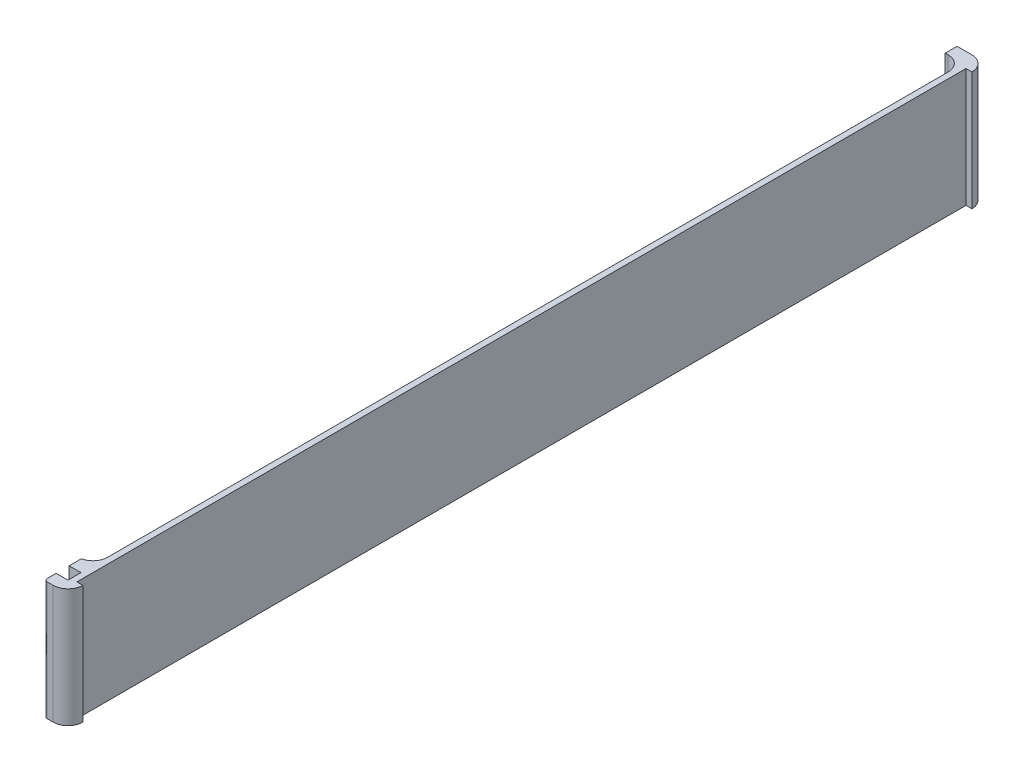
SolidWorks part; units mm, degrees
ref_plane "Front Plane" through (0, 0, 0) normal (0, 0, 1) x (1, 0, 0)
ref_plane "Top Plane" through (0, 0, 0) normal (0, 1, 0) x (1, 0, 0)
ref_plane "Right Plane" through (0, 0, 0) normal (1, 0, 0) x (0, 0, -1)
sketch "Sketch1" plane through (0, 0, 0) normal (0, 1, 0) x (1, 0, 0)
  line L1 (-19.5, 77.5) -> (19.5, 77.5)
  line L2 (-19.5, 77.5) -> (-19.5, -77.5)
  line L3 (-19.5, -77.5) -> (19.5, -77.5)
  line L4 (19.5, 77.5) -> (19.5, -77.5)
  line L5 (-19.5, 77.5) -> (19.5, -77.5) construction
  line L6 (-19.5, -77.5) -> (19.5, 77.5) construction
  point P0 (0, 0)
  dimension "D1" = 39
  dimension "D2" = 155
extrude "Boss-Extrude1" add sketch "Sketch1" along normal blind 2
sketch "Sketch2" plane through (0, 2, 0) normal (0, 1, 0) x (1, 0, 0)
  line L0 (-17.5, -75.5) -> (-17.5, -77.5)
  line L1 (-19.5, 77.5) -> (19.5, 77.5)
  line L2 (-19.5, 77.5) -> (-19.5, -77.5)
  line L3 (-19.5, -77.5) -> (19.5, -77.5)
  line L4 (19.5, 77.5) -> (19.5, -77.5)
  line L5 (-17.5, 75.5) -> (17.5, 75.5)
  line L6 (-17.5, 75.5) -> (-17.5, -75.5)
  line L7 (-17.5, -75.5) -> (17.5, -75.5)
  line L8 (17.5, 75.5) -> (17.5, -75.5)
  line L9 (-17.5, 75.5) -> (17.5, -75.5) construction
  line L10 (-17.5, -75.5) -> (17.5, 75.5) construction
  line L11 (17.5, -75.5) -> (17.5, -77.5)
  point P6 (0, 0)
  line M9 (19.5, -77.5) -> (19.5, 77.5)
  line M10 (19.5, 77.5) -> (-19.5, 77.5)
  line M11 (-19.5, 77.5) -> (-19.5, -77.5)
  line M12 (-19.5, -77.5) -> (19.5, -77.5)
  dimension "D1" = 2
  dimension "D2" = 2
extrude "Boss-Extrude2" add sketch "Sketch2" along normal blind 38 contours L8 L11 L3 L0 L6 L5 M9 M10 M11 M12 region at (-19.0983, 2, 76.5)
sketch "Sketch3" plane through (0, 2, 0) normal (0, 1, 0) x (1, 0, 0)
  line L0 (-17.5, 75.5) -> (-17.5, -77.5) construction
  line L1 (-17.5, -77.5) -> (-15.5, -77.5)
  line L2 (-17.5, -77.5) -> (-17.5, -75.5)
  line L3 (-17.5, -75.5) -> (-15.5, -75.5)
  line L4 (-15.5, -77.5) -> (-15.5, -75.5)
  line L5 (-17.5, -73.3) -> (-15.5, -73.3)
  line L6 (-17.5, -73.3) -> (-17.5, -71.3)
  line L7 (-17.5, -71.3) -> (-15.5, -71.3)
  line L8 (-15.5, -73.3) -> (-15.5, -71.3)
  line L9 (17.5, 75.5) -> (17.5, -77.5) construction
  line L10 (17.5, -77.5) -> (15.5, -77.5)
  line L11 (17.5, -77.5) -> (17.5, -75.5)
  line L12 (17.5, -75.5) -> (15.5, -75.5)
  line L13 (15.5, -77.5) -> (15.5, -75.5)
  line L14 (17.5, -73.3) -> (15.5, -73.3)
  line L15 (17.5, -73.3) -> (17.5, -71.3)
  line L16 (17.5, -71.3) -> (15.5, -71.3)
  line L17 (15.5, -73.3) -> (15.5, -71.3)
  line L18 (15.5, -75.5) -> (15.5, -73.3) construction
  line L19 (-15.5, -73.3) -> (15.5, -73.3) construction
  line L20 (-15.5, -75.5) -> (-15.5, -73.3) construction
  line L21 (-15.5, -75.5) -> (15.5, -75.5) construction
  line L22 (15.5, -71.3) -> (-15.5, -71.3) construction
  dimension "D1" = 2
  dimension "D2" = 2
  dimension "D3" = 2.2
  dimension "D4" = 2
extrude "Boss-Extrude3" add sketch "Sketch3" along normal up to surface (38 mm away) up to face at (0, 40, 0.5)
sketch "Sketch4" plane through (0, 0, -75.5) normal (0, 0, 1) x (1, 0, 0)
  line L0 (-17.5, 40) -> (-15.5, 40)
  line L1 (-17.5, 40) -> (17.5, 40) construction
  line L2 (-15.5, 40) -> (-15.5, 38)
  line L3 (-15.5, 38) -> (-17.5, 38)
  line L5 (-17.5, 38) -> (-17.5, 40)
  line L7 (-17.5, 40) -> (-17.5, 2) construction
  line L8 (-15.5, 33.8) -> (-17.5, 31.8)
  line L9 (-17.5, 31.8) -> (-17.5, 35.8)
  line L10 (-15.5, 33.8) -> (-15.5, 35.8)
  line L11 (-15.5, 35.8) -> (-17.5, 35.8)
  line L12 (0, 0) -> (0, 40) construction
  line L13 (15.5, 35.8) -> (17.5, 35.8)
  line L14 (15.5, 33.8) -> (15.5, 35.8)
  line L15 (17.5, 31.8) -> (17.5, 35.8)
  line L16 (15.5, 33.8) -> (17.5, 31.8)
  line L17 (17.5, 38) -> (17.5, 40)
  line L18 (15.5, 38) -> (17.5, 38)
  line L19 (15.5, 40) -> (15.5, 38)
  line L20 (17.5, 40) -> (15.5, 40)
  dimension "D1" = 2
  dimension "D2" = 2
  dimension "D3" = 45
  dimension "D4" = 2.2
  dimension "D5" = 2
extrude "Boss-Extrude4" add sketch "Sketch4" along normal up to surface (153 mm away)
sketch "Sketch5" plane through (0, 2, 0) normal (0, 1, 0) x (1, 0, 0)
  line L1 (-15.5, -77.5) -> (15.5, -77.5)
  line L2 (-15.5, -77.5) -> (-15.5, -75.5)
  line L3 (-15.5, -75.5) -> (15.5, -75.5)
  line L4 (15.5, -77.5) -> (15.5, -75.5)
  line L5 (-15.5, -71.3) -> (15.5, -71.3)
  line L6 (-15.5, -71.3) -> (-15.5, -73.3)
  line L7 (-15.5, -73.3) -> (15.5, -73.3)
  line L8 (15.5, -71.3) -> (15.5, -73.3)
sketch "Sketch6" plane through (0, 0, -75.5) normal (0, 0, 1) x (1, 0, 0)
  line L0 (-17.5, 38) -> (-15.5, 38) construction
  line L1 (-17.5, 38) -> (17.5, 38)
  line L2 (-17.5, 38) -> (-17.5, 35.8)
  line L3 (-17.5, 35.8) -> (17.5, 35.8)
  line L4 (17.5, 38) -> (17.5, 35.8)
  line L5 (-17.5, 38) -> (-17.5, 35.8) construction
  line L6 (-15.5, 35.8) -> (-17.5, 35.8) construction
extrude "Cut-Extrude1" cut sketch "Sketch6" along normal through all
sketch "Sketch7" plane through (0, 2, 0) normal (0, 1, 0) x (1, 0, 0)
  line L1 (-17.5, -75.5) -> (17.5, -75.5)
  line L2 (-17.5, -75.5) -> (-17.5, -73.3)
  line L3 (-17.5, -73.3) -> (17.5, -73.3)
  line L4 (17.5, -75.5) -> (17.5, -73.3)
extrude "Cut-Extrude2" cut sketch "Sketch7" along normal through all
extrude "Boss-Extrude5" add sketch "Sketch5" along normal blind 2
sketch "Sketch8" plane through (0, 0, 0) normal (1, 0, 0) x (0, 0, -1)
  line L0 (75.5, 40) -> (73.5, 40)
  line L1 (-73.3, 40) -> (75.5, 40) construction
  line L2 (73.5, 40) -> (73.5, 38)
  line L3 (-73.3, 38) -> (75.5, 38) construction
  line L4 (73.5, 38) -> (75.5, 38)
  line L5 (75.5, 38) -> (75.5, 40)
  line L6 (75.5, 35.8) -> (73.5, 35.8)
  line L7 (-73.3, 35.8) -> (75.5, 35.8) construction
  line L8 (73.5, 35.8) -> (73.5, 33.8)
  line L9 (-71.3, 33.8) -> (75.5, 33.8) construction
  line L10 (73.5, 33.8) -> (75.5, 31.8)
  line L11 (75.5, 31.8) -> (75.5, 35.8)
  dimension "D1" = 2
extrude "Boss-Extrude6" add sketch "Sketch8" along normal up to surface and the other way up to surface up to face at (17.5, 16.9, -2.1) other way up to face at (-17.5, 16.9, -2.1)
sketch "Sketch10" plane through (-17.5, 0, 0) normal (1, 0, 0) x (0, 0, -1)
  line L1 (-75.5, 35.8) -> (-77.5, 35.8)
  line L2 (-75.5, 35.8) -> (-75.5, 38)
  line L3 (-75.5, 38) -> (-77.5, 38)
  line L4 (-77.5, 35.8) -> (-77.5, 38)
  line L5 (-73.3, 40) -> (-75.5, 40)
  line L6 (-73.3, 40) -> (-73.3, 38)
  line L7 (-73.3, 38) -> (-75.5, 38)
  line L8 (-75.5, 40) -> (-75.5, 38)
  line M1 (-75.5, 40) -> (-75.5, 38)
  line M2 (-75.5, 38) -> (-77.5, 38)
  line M3 (-77.5, 38) -> (-77.5, 35.8)
  line M4 (-77.5, 35.8) -> (-75.5, 35.8)
  line M11 (-73.3, 38) -> (-73.3, 40)
  line M12 (-73.3, 40) -> (-75.5, 40)
extrude "Boss-Extrude8" add sketch "Sketch10" along normal up to surface (2 mm away) contours L2 M4 M2 M3 | L7 M11 M12 M1 region at (-17.5, 39, 74.4) region at (-17.5, 36.9, 76.5) up to face at (-15.5, 39, -0.1)
sketch "Sketch11" plane through (17.5, 0, 0) normal (-1, 0, 0) x (0, 0, 1)
  line L1 (75.5, 35.8) -> (77.5, 35.8)
  line L2 (75.5, 35.8) -> (75.5, 38)
  line L3 (75.5, 38) -> (77.5, 38)
  line L4 (77.5, 35.8) -> (77.5, 38)
  line L5 (73.3, 40) -> (75.5, 40)
  line L6 (73.3, 40) -> (73.3, 38)
  line L7 (73.3, 38) -> (75.5, 38)
  line L8 (75.5, 40) -> (75.5, 38)
  line M2 (75.5, 35.8) -> (77.5, 35.8)
  line M3 (77.5, 35.8) -> (77.5, 38)
  line M4 (77.5, 38) -> (75.5, 38)
  line M5 (75.5, 38) -> (75.5, 40)
  line M6 (75.5, 40) -> (73.3, 40)
  line M7 (73.3, 40) -> (73.3, 38)
extrude "Boss-Extrude9" add sketch "Sketch11" along normal up to surface (2 mm away) contours L2 M2 M3 M4 | L7 M7 M5 M6 region at (17.5, 36.9, 76.5) region at (17.5, 39, 74.4) up to face at (15.5, 39, -0.1)
fillet "Fillet2" radius 2.5 17 edges at (-17.5, 16.9, 71.3) (17.5, 16.9, 71.3) (19.5, 20, 77.5) (-19.5, 20, 77.5) (-19.5, 20, -77.5) (-17.5, 16.9, -75.5) (17.5, 16.9, -75.5) (19.5, 20, -77.5) (-19.5, 40, 0) (0, 40, -77.5) (19.5, 40, 0) (0, 0, -77.5) (0, 0, 77.5) (-19.5, 0, 0) (19.5, 0, 0) (-17.5, 40, 77.5) (17.5, 40, 77.5)
sketch "Sketch13" plane through (0, 0, -77.5) normal (0, 0, -1) x (-1, 0, 0)
  line L0 (15.5, 37.5) -> (15.5, 4) construction
  line L1 (-15.5, 7) -> (15.5, 7)
  line L2 (-15.5, 7) -> (-15.5, 4)
  line L3 (-15.5, 4) -> (15.5, 4)
  line L4 (15.5, 7) -> (15.5, 4)
  dimension "D1" = 3
sketch "Sketch14" plane through (0, 0, -75.5) normal (0, 0, 1) x (1, 0, 0)
  line L1 (-18.25, 9) -> (18.25, 9)
  line L2 (-18.25, 9) -> (-18.25, 1.25)
  line L3 (-18.25, 1.25) -> (18.25, 1.25)
  line L4 (18.25, 9) -> (18.25, 1.25)
  line L5 (15.5, 7) -> (-15.5, 7) construction
  line L7 (17, 0) -> (17, 2.5) construction
  line L8 (19.5, 2.5) -> (17, 2.5) construction
  line L10 (-19.5, 2.5) -> (-17, 2.5) construction
  point P20 (17, 1.25)
  point P23 (18.25, 2.5)
  point P26 (-18.25, 2.5)
  dimension "D1" = 2
extrude "Boss-Extrude10" add sketch "Sketch14" along normal blind 2
extrude "Cut-Extrude4" cut sketch "Sketch13" against normal blind 2
fillet "Fillet3" radius 2 1 edges at (0, 9, -73.5)
fillet "Fillet4" radius 0.5 12 edges at (0, 4, -77.5) (0, 7, -77.5) (15.5, 7, -76.5) (15.5, 4, -76.5) (15.5, 5.5, -77.5) (-15.5, 4, -76.5) (-15.5, 7, -76.5) (-15.5, 5.5, -77.5) (0, 7, -75.5) (-15.5, 5.5, -75.5) (0, 4, -75.5) (15.5, 5.5, -75.5)
sketch "Sketch15" plane through (0, 0, 0) normal (0, -1, 0) x (1, 0, 0)
  line L0 (0, 77.5) -> (0, 0) construction
  line L1 (-17, 77.5) -> (17, 77.5) construction
  line L2 (0, 0) -> (0, -77.5) construction
  line L4 (17, -77.5) -> (-17, -77.5) construction
  circle A0 centre (0, 38.75) radius 5.1
  circle A1 centre (0, -38.75) radius 5.1
  dimension "D1" = 10.2
extrude "Cut-Extrude5" cut sketch "Sketch15" against normal through all
sketch "Sketch16" plane through (0, 2, 0) normal (0, 1, 0) x (1, 0, 0)
  circle A0 centre (0, 38.75) radius 7.1
  circle A1 centre (0, -38.75) radius 7.1
  circle A2 centre (0, 38.75) radius 5.1 construction
  dimension "D1" = 2
extrude "Boss-Extrude11" add sketch "Sketch16" along normal blind 1
fillet "Fillet5" radius 0.5 4 edges at (0, 2, 45.85) (0, 2, -31.65) (0, 3, 45.85) (0, 3, -31.65)
sketch "Sketch12" plane through (0, 0, -75.5) normal (0, 0, 1) x (1, 0, 0)
  line L0 (0, 0) -> (0, 40) construction
  line L1 (15.5, 40) -> (-15.5, 40) construction
  line L2 (0, 20) -> (-10, 20)
  line L3 (0, 20) -> (-9.0097, 15.6612)
  line L4 (0, 20) -> (-6.2349, 12.1817)
  line L5 (0, 20) -> (-2.2252, 10.2507)
  line L6 (0, 20) -> (2.2252, 10.2507)
  line L7 (0, 20) -> (6.2349, 12.1817)
  line L8 (0, 20) -> (9.0097, 15.6612)
  line L9 (0, 20) -> (10, 20)
  line L10 (0, 20) -> (9.0097, 24.3388)
  line L11 (0, 20) -> (6.2349, 27.8183)
  line L12 (0, 20) -> (2.2252, 29.7493)
  line L13 (0, 20) -> (-2.2252, 29.7493)
  line L14 (0, 20) -> (-6.2349, 27.8183)
  line L15 (0, 20) -> (-9.0097, 24.3388)
  circle A0 centre (0, 20) radius 10
  circle A1 centre (0, 20) radius 7.5
  circle A2 centre (0, 20) radius 5
  circle A3 centre (0, 20) radius 2.5
  point P26 (0, 20)
  dimension "D1" = 20
  dimension "D2" = 2.5
  dimension "D3" = 2.5
  dimension "D4" = 2.5
  dimension "D5" = 14
extrude "Cut-Extrude3" cut sketch "Sketch12" against normal through all contours A1 L6 A0 L7 | A1 L4 A0 L5 | A1 L2 A0 L3 | A1 L14 A0 L15 | A1 L0 A0 L13 | L0 A1 L12 A0 | A1 L10 A0 L11 | A1 L8 A0 L9 | A3 L8 A2 L9 | A3 L10 A2 L11 | L0 A3 L12 A2 | A3 L0 A2 L13 | A3 L14 A2 L15 | A3 L2 A2 L3 | A3 L4 A2 L5 | A3 L6 A2 L7 region at (-3.7903, 12.1293, -75.5) region at (3.7903, 12.1293, -75.5) region at (-1.6732, 16.5256, -75.5) region at (1.6732, 16.5256, -75.5) region at (-8.5168, 18.0561, -75.5) region at (8.5168, 18.0561, -75.5) region at (-0.4345, 23.8563, -75.5) region at (0.4345, 23.8563, -75.5) region at (-3.7596, 19.1419, -75.5) region at (3.7596, 19.1419, -75.5) region at (3.015, 22.4044, -75.5) region at (-3.015, 22.4044, -75.5) region at (-6.8299, 25.4467, -75.5) region at (6.8299, 25.4467, -75.5) region at (-0.9843, 28.7358, -75.5) region at (0.9843, 28.7358, -75.5)
fillet "Fillet6" radius 0.4 112 edges at (5.4555, 26.841, -77.5) (7.8183, 26.2349, -77.5) (7.8835, 23.7965, -77.5) (5.8637, 24.6762, -77.5) (3.75, 20, -77.5) (4.8746, 18.8874, -77.5) (3.3786, 18.3729, -77.5) (2.4373, 19.4437, -77.5) (-1.9471, 28.5306, -77.5) (0, 30, -77.5) (1.9471, 28.5306, -77.5) (0, 27.5, -77.5) (-7.8835, 16.2035, -77.5) (-9.7493, 17.7748, -77.5) (-8.75, 20, -77.5) (-7.312, 18.3311, -77.5) (2.3381, 17.0681, -77.5) (2.1694, 15.4952, -77.5) (0.8345, 16.344, -77.5) (1.0847, 17.7476, -77.5) (-0.8345, 16.344, -77.5) (-2.1694, 15.4952, -77.5) (-2.3381, 17.0681, -77.5) (-1.0847, 17.7476, -77.5) (5.4555, 13.159, -77.5) (4.3388, 10.9903, -77.5) (1.9471, 11.4694, -77.5) (3.2541, 13.2427, -77.5) (0, 22.5, -77.5) (-0.8345, 23.656, -77.5) (0, 25, -77.5) (0.8345, 23.656, -77.5) (-3.3786, 21.6271, -77.5) (-3.9092, 23.1174, -77.5) (-2.3381, 22.9319, -77.5) (-1.9546, 21.5587, -77.5) (-3.3786, 18.3729, -77.5) (-4.8746, 18.8874, -77.5) (-3.75, 20, -77.5) (-2.4373, 19.4437, -77.5) (-1.9471, 11.4694, -77.5) (-4.3388, 10.9903, -77.5) (-5.4555, 13.159, -77.5) (-3.2541, 13.2427, -77.5) (-7.8835, 23.7965, -77.5) (-7.8183, 26.2349, -77.5) (-5.4555, 26.841, -77.5) (-5.8637, 24.6762, -77.5) (2.3381, 22.9319, -77.5) (3.9092, 23.1174, -77.5) (3.3786, 21.6271, -77.5) (1.9546, 21.5587, -77.5) (8.75, 20, -77.5) (9.7493, 17.7748, -77.5) (7.8835, 16.2035, -77.5) (7.312, 18.3311, -77.5) (7.8835, 23.7965, -75.5) (7.8183, 26.2349, -75.5) (5.4555, 26.841, -75.5) (5.8637, 24.6762, -75.5) (3.3786, 18.3729, -75.5) (4.8746, 18.8874, -75.5) (3.75, 20, -75.5) (2.4373, 19.4437, -75.5) (1.9471, 28.5306, -75.5) (0, 30, -75.5) (-1.9471, 28.5306, -75.5) (0, 27.5, -75.5) (-8.75, 20, -75.5) (-9.7493, 17.7748, -75.5) (-7.8835, 16.2035, -75.5) (-7.312, 18.3311, -75.5) (0.8345, 16.344, -75.5) (2.1694, 15.4952, -75.5) (2.3381, 17.0681, -75.5) (1.0847, 17.7476, -75.5) (-2.3381, 17.0681, -75.5) (-2.1694, 15.4952, -75.5) (-0.8345, 16.344, -75.5) (-1.0847, 17.7476, -75.5) (1.9471, 11.4694, -75.5) (4.3388, 10.9903, -75.5) (5.4555, 13.159, -75.5) (3.2541, 13.2427, -75.5) (0, 22.5, -75.5) (0.8345, 23.656, -75.5) (0, 25, -75.5) (-0.8345, 23.656, -75.5) (-2.3381, 22.9319, -75.5) (-3.9092, 23.1174, -75.5) (-3.3786, 21.6271, -75.5) (-1.9546, 21.5587, -75.5) (-3.75, 20, -75.5) (-4.8746, 18.8874, -75.5) (-3.3786, 18.3729, -75.5) (-2.4373, 19.4437, -75.5) (-5.4555, 13.159, -75.5) (-4.3388, 10.9903, -75.5) (-1.9471, 11.4694, -75.5) (-3.2541, 13.2427, -75.5) (-5.4555, 26.841, -75.5) (-7.8183, 26.2349, -75.5) (-7.8835, 23.7965, -75.5) (-5.8637, 24.6762, -75.5) (3.3786, 21.6271, -75.5) (3.9092, 23.1174, -75.5) (2.3381, 22.9319, -75.5) (7.8835, 16.2035, -75.5) (9.7493, 17.7748, -75.5) (8.75, 20, -75.5) (7.312, 18.3311, -75.5) (1.9546, 21.5587, -75.5)
fillet "Fillet7" radius 0.5 8 edges at (15.5, 40, 0.75) (15.5, 39.2678, 76.7678) (-15.5, 40, 0.75) (-15.5, 39.2678, 76.7678) (0, 40, -73.5) (15.5, 20.75, 77.5) (-15.5, 20.75, 77.5) (0, 4, 77.5)
sketch "Sketch17" plane through (0, 0, 0) normal (0, -1, 0) x (1, 0, 0)
  line L0 (-17, -77.5) -> (-17, 70.3)
  line L1 (-17, -77.5) -> (17, -77.5)
  line L2 (17, -77.5) -> (17, 70.3)
  line L3 (17, -75) -> (17, 75) construction
  line L5 (17, 70.3) -> (15, 71.3)
  line L6 (15, 71.3) -> (15, 77.5)
  line L7 (15, 77.5) -> (-15, 77.5)
  line L8 (-15, 77.5) -> (-15, 71.3)
  line L9 (-15, 71.3) -> (-17, 70.3)
  line L10 (-17, 75) -> (-17, -75) construction
  line L12 (-15, 71.3) -> (15, 71.3) construction
  line L13 (17, 70.3) -> (-17, 70.3) construction
  line L14 (0, 71.3) -> (0, 77.5) construction
  line L15 (-17, 77.5) -> (17, 77.5) construction
  arc A0 (-19.5, -75) -> (-17, -77.5) centre (-17, -75) ccw construction
  dimension "D1" = 1
  dimension "D2" = 30
  dimension "D3" = 6.2
extrude "Cut-Extrude6" cut sketch "Sketch17" against normal blind 6
sketch "Sketch18" plane through (0, 0, 0) normal (0, 0, 1) x (1, 0, 0)
  line L0 (15, 9) -> (-15, 9) construction
  line L1 (-14.5, 9) -> (14.5, 9)
  line L2 (-14.5, 9) -> (-14.5, 6)
  line L3 (-14.5, 6) -> (14.5, 6)
  line L4 (14.5, 9) -> (14.5, 6)
  line L5 (-17, 6) -> (17, 6) construction
  line L6 (0, 6) -> (0, 0) construction
  dimension "D1" = 29
extrude "Cut-Extrude8" cut sketch "Sketch18" against normal through all
sketch "Sketch20" plane through (0, 0, 0) normal (0, 0, 1) x (1, 0, 0)
  line L0 (-16, 40) -> (16, 40) construction
  line L1 (-19.5, 40) -> (-14.5, 40)
  line L2 (-19.5, 40) -> (-19.5, 0)
  line L3 (-19.5, 0) -> (-14.5, 0)
  line L4 (-14.5, 40) -> (-14.5, 0)
  line L5 (-14.5, 6) -> (14.5, 6)
  line L6 (-14.5, 6) -> (-14.5, 40)
  line L7 (-14.5, 40) -> (14.5, 40)
  line L8 (14.5, 6) -> (14.5, 40)
  line L9 (14.5, 40) -> (19.5, 40)
  line L10 (14.5, 40) -> (14.5, 0)
  line L11 (14.5, 0) -> (19.5, 0)
  line L12 (19.5, 40) -> (19.5, 0)
  line L13 (-15, 0) -> (-17, 0) construction
  line L14 (-19.5, 2.5) -> (-19.5, 37.5) construction
  line L15 (17, 0) -> (15, 0) construction
  line L16 (19.5, 37.5) -> (19.5, 2.5) construction
extrude "Cut-Extrude11" cut sketch "Sketch20" against normal through all both and the other way through all contours L5 L8 L7 L4 | L1 L2 L3 L4 region at (0, 23, 0)
sketch "Sketch21" plane through (0, 0, 0) normal (1, 0, 0) x (0, 0, -1)
  line L1 (-77.5, 40) -> (77.5, 40)
  line L2 (-77.5, 40) -> (-77.5, 30)
  line L3 (-77.5, 30) -> (77.5, 30)
  line L4 (77.5, 40) -> (77.5, 30)
  line L5 (77.5, 30) -> (-77.5, 30)
  line L6 (77.5, 30) -> (77.5, 10)
  line L7 (77.5, 10) -> (-77.5, 10)
  line L8 (-77.5, 30) -> (-77.5, 10)
  line L9 (-77.5, 10) -> (77.5, 10)
  line L10 (-77.5, 10) -> (-77.5, 0)
  line L11 (-77.5, 0) -> (77.5, 0)
  line L12 (77.5, 10) -> (77.5, 0)
  line L16 (77.5, 30) -> (77.5, 10)
  line L17 (-77.5, 10) -> (-77.5, 30)
  line L18 (77.5, 37.5) -> (77.5, 6) construction
  line L19 (-75, 40) -> (75, 40) construction
  line L20 (-77.5, 2.5) -> (-77.5, 37.5) construction
  line L21 (75, 0) -> (-70.3, 0) construction
  dimension "D1" = 20
  dimension "D2" = 10
extrude "Cut-Extrude12" cut sketch "Sketch21" along normal through all contours L4 L1 L2 L3 | L12 L7 L10 L11 region at (0, 35, 0) region at (0, 5, 0)
sketch "Sketch22" plane through (19.5, 0, 0) normal (1, 0, 0) x (0, 0, -1)
  line L1 (75, 10) -> (-75, 10)
  line L2 (75, 10) -> (75, 30)
  line L3 (75, 30) -> (-75, 30)
  line L4 (-75, 10) -> (-75, 30)
  line L5 (75, 10) -> (-75, 30) construction
  line L6 (75, 30) -> (-75, 10) construction
  point P0 (0, 20)
  point P6 (75, 10)
extrude "Cut-Extrude13" cut sketch "Sketch22" against normal blind 1
